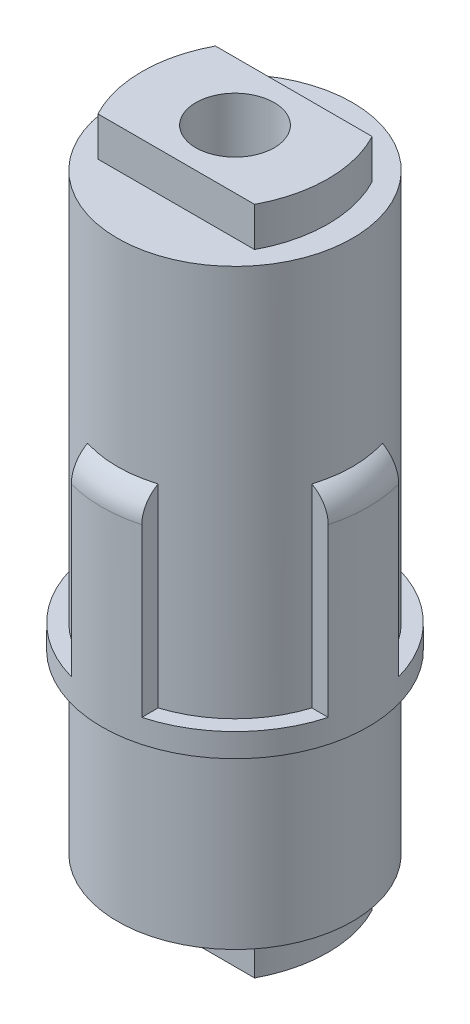
SolidWorks part; units mm, degrees
ref_plane "Front Plane" through (0, 0, 0) normal (0, 0, 1) x (1, 0, 0)
ref_plane "Top Plane" through (0, 0, 0) normal (0, 1, 0) x (1, 0, 0)
ref_plane "Right Plane" through (0, 0, 0) normal (1, 0, 0) x (0, 0, -1)
sketch "Sketch1" plane through (0, 0, 0) normal (0, 1, 0) x (1, 0, 0)
  circle A0 centre (0, 0) radius 7.25
  dimension "D1" = 14.5
extrude "Boss-Extrude1" add sketch "Sketch1" along normal blind 25
sketch "Sketch2" plane through (0, 25, 0) normal (0, 1, 0) x (1, 0, 0)
  line L0 (0, 3.65) -> (0, -3.65) construction
  line L1 (-4.9, -3.65) -> (4.9, -3.65)
  line L3 (-4.9, 3.65) -> (4.9, 3.65)
  line L5 (-4.9, -3.65) -> (4.9, 3.65) construction
  line L6 (-4.9, 3.65) -> (4.9, -3.65) construction
  circle A0 centre (0, 0) radius 2.1
  arc A1 (-4.9, 3.65) -> (-4.9, -3.65) centre (2.2188, 0) ccw
  arc A2 (4.9, 3.65) -> (4.9, -3.65) centre (-2.2188, 0) cw
  point P0 (0, 0)
  dimension "D3" = 4.2
  dimension "D4" = 8
  dimension "D1" = 9.8
  dimension "D2" = 7.3
extrude "Boss-Extrude2" add sketch "Sketch2" along normal blind 2.5
sketch "Sketch4" plane through (0, 0, 0) normal (0, -1, 0) x (-1, 0, 0)
  circle A0 centre (0, 0) radius 8.5
  dimension "D1" = 17
extrude "Boss-Extrude3" add sketch "Sketch4" along normal blind 1.5
sketch "Sketch5" plane through (0, 0, 0) normal (0, 1, 0) x (1, 0, 0)
  line L0 (0, 8.5) -> (0, -8.5) construction
  line L1 (-8.5, 0) -> (8.5, 0) construction
  line L2 (-2.25, 8.1968) -> (-2.25, 6.892)
  line L3 (6.892, 2.25) -> (8.1968, 2.25)
  line L4 (2.25, 8.1968) -> (2.25, 6.892)
  line L5 (6.892, -2.25) -> (8.1968, -2.25)
  line L6 (2.25, -8.1968) -> (2.25, -6.892)
  line L7 (-2.25, -8.1968) -> (-2.25, -6.892)
  line L8 (-6.892, -2.25) -> (-8.1968, -2.25)
  line L9 (-6.892, 2.25) -> (-8.1968, 2.25)
  circle A0 centre (0, 0) radius 8.5 construction
  circle A1 centre (0, 0) radius 7.25 construction
  circle A2 centre (0, 0) radius 7.25 construction
  arc A3 (-8.1968, 2.25) -> (-8.1968, -2.25) centre (0, 0) ccw
  arc A4 (-6.892, 2.25) -> (-6.892, -2.25) centre (0, 0) ccw
  arc A5 (2.25, 8.1968) -> (-2.25, 8.1968) centre (0, 0) ccw
  arc A6 (2.25, 6.892) -> (-2.25, 6.892) centre (0, 0) ccw
  arc A7 (8.1968, -2.25) -> (8.1968, 2.25) centre (0, 0) ccw
  arc A8 (6.892, -2.25) -> (6.892, 2.25) centre (0, 0) ccw
  arc A9 (-2.25, -8.1968) -> (2.25, -8.1968) centre (0, 0) ccw
  arc A10 (-2.25, -6.892) -> (2.25, -6.892) centre (0, 0) ccw
  dimension "D1" = 2.25
  dimension "D2" = 2.25
extrude "Boss-Extrude5" add sketch "Sketch5" along normal blind 12.5
fillet "Fillet2" radius 2 4 edges at (-8.5, 12.5, 0) (0, 12.5, -8.5) (8.5, 12.5, 0) (0, 12.5, 8.5)
sketch "Sketch6" plane through (0, -1.5, 0) normal (0, -1, 0) x (-1, 0, 0)
  circle A0 centre (0, 0) radius 7.25
  dimension "D1" = 14.5
extrude "Boss-Extrude6" add sketch "Sketch6" along normal blind 11.25
sketch "Sketch7" plane through (0, -12.75, 0) normal (0, -1, 0) x (-1, 0, 0)
  line L1 (4.9, 3.65) -> (-4.9, 3.65)
  line L3 (4.9, -3.65) -> (-4.9, -3.65)
  circle A0 centre (0, 0) radius 2.1
  arc A1 (4.9, -3.65) -> (4.9, 3.65) centre (-2.2188, 0) ccw
  arc A2 (-4.9, -3.65) -> (-4.9, 3.65) centre (2.2188, 0) cw
extrude "Boss-Extrude7" add sketch "Sketch7" along normal blind 2.5 contours L1 A2 L3 A1 | A0
sketch "Sketch8" plane through (0, -12.75, 0) normal (0, -1, 0) x (-1, 0, 0)
  circle A0 centre (0, 0) radius 2.1
extrude "Cut-Extrude1" cut sketch "Sketch8" against normal blind 53.5
sketch "Sketch9" plane through (0, -1.5, 0) normal (0, -1, 0) x (1, 0, 0)
  circle A0 centre (0, 0) radius 7.5
  circle A1 centre (0, 0) radius 7.25
  dimension "D1" = 15
extrude "Boss-Extrude8" add sketch "Sketch9" along normal up to surface (11.25 mm away) up to face at (0, -12.75, 0)
sketch "Sketch10" plane through (0, 0, 0) normal (0, 1, 0) x (1, 0, 0)
  circle A0 centre (0, 0) radius 7.5
  circle A1 centre (0, 0) radius 7.25
  dimension "D1" = 15
extrude "Boss-Extrude9" add sketch "Sketch10" along normal up to surface (25 mm away) up to face at (0, 25, 0)
sketch "Sketch11" plane through (0, 27.5, 0) normal (0, 1, 0) x (1, 0, 0)
  circle A0 centre (0, 0) radius 2.15
  dimension "D1" = 4.3
extrude "Cut-Extrude2" cut sketch "Sketch11" against normal blind 50 contours A0
sketch "Sketch12" plane through (0, -15.25, 0) normal (0, -1, 0) x (-1, 0, 0)
  circle A0 centre (0, 0) radius 6.6073
extrude "Cut-Extrude3" cut sketch "Sketch12" against normal up to surface (2.5 mm away) up to face at (0, -12.75, 0)
sketch "Sketch13" plane through (0, 27.5, 0) normal (0, 1, 0) x (1, 0, 0)
  circle A0 centre (0, 0) radius 6.7565
extrude "Cut-Extrude4" cut sketch "Sketch13" against normal up to surface (2.5 mm away) up to face at (0, 25, 0)
sketch "Sketch14" plane through (0, -12.75, 0) normal (0, -1, 0) x (-1, 0, 0)
  line L1 (5, 3.75) -> (-5, 3.75)
  line L2 (5, 3.75) -> (5, -3.75)
  line L3 (5, -3.75) -> (-5, -3.75)
  line L4 (-5, 3.75) -> (-5, -3.75)
  line L5 (5, 3.75) -> (-5, -3.75) construction
  line L6 (5, -3.75) -> (-5, 3.75) construction
  arc A0 (5, -3.75) -> (5, 3.75) centre (-2.0666, 0) ccw
  arc A1 (-5, -3.75) -> (-5, 3.75) centre (2.0666, 0) cw
  point P0 (0, 0)
  circle M4 centre (0, 0) radius 2.15
  dimension "D3" = 8
  dimension "D4" = 8
  dimension "D1" = 10
  dimension "D2" = 7.5
extrude "Boss-Extrude10" add sketch "Sketch14" along normal blind 2.5 contours L1 L4 L3 L2 M4 | L2 A0 | A1 L4 region at (-4.875, -12.75, 0) region at (-5.3753, -12.75, 0) region at (5.3753, -12.75, 0)
sketch "Sketch15" plane through (0, 25, 0) normal (0, 1, 0) x (1, 0, 0)
  line L0 (0, 3.75) -> (0, -3.75) construction
  line L1 (-5, -3.75) -> (5, -3.75)
  line L3 (-5, 3.75) -> (5, 3.75)
  line L5 (-5, -3.75) -> (5, 3.75) construction
  line L6 (-5, 3.75) -> (5, -3.75) construction
  arc A0 (-5, 3.75) -> (-5, -3.75) centre (2.0666, 0) ccw
  arc A1 (5, 3.75) -> (5, -3.75) centre (-2.0666, 0) cw
  circle A2 centre (0, 0) radius 2.5
  point P0 (0, 0)
  dimension "D3" = 8
  dimension "D4" = 5
  dimension "D1" = 10
  dimension "D2" = 7.5
extrude "Boss-Extrude11" add sketch "Sketch15" along normal blind 2.5
sketch "Sketch16" plane through (0, 25, 0) normal (0, 1, 0) x (1, 0, 0)
  circle A0 centre (0, 0) radius 2.5
extrude "Cut-Extrude5" cut sketch "Sketch16" against normal blind 61.5
